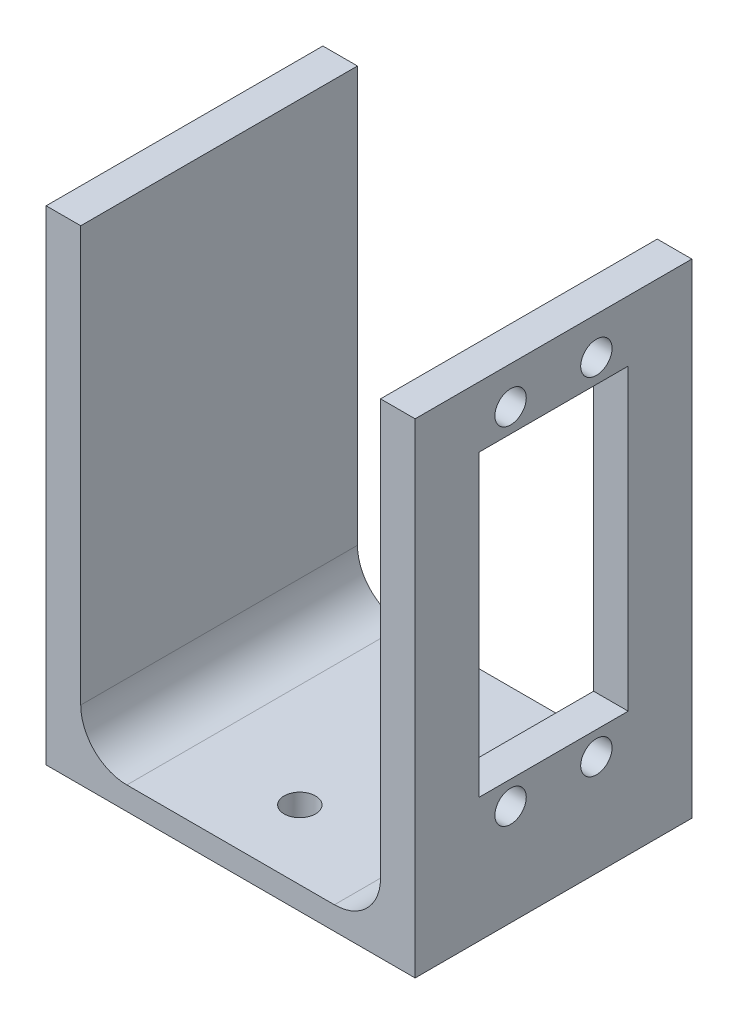
SolidWorks part; units mm, degrees
ref_plane "Front" through (0, 0, 0) normal (0, 0, 1) x (1, 0, 0)
ref_plane "Top" through (0, 0, 0) normal (0, 1, 0) x (1, 0, 0)
ref_plane "Right" through (0, 0, 0) normal (1, 0, 0) x (0, 0, -1)
sketch "Sketch1" plane through (0, 0, 0) normal (0, 1, 0) x (1, 0, 0)
  line L1 (0, 0) -> (50.8, 0)
  line L2 (0, 0) -> (0, 38.1)
  line L3 (0, 38.1) -> (50.8, 38.1)
  line L4 (50.8, 0) -> (50.8, 38.1)
  dimension "D1" = 38.1
  dimension "D2" = 50.8
extrude "Boss-Extrude1" add sketch "Sketch1" along normal blind 3.175
sketch "Sketch2" plane through (0, 3.175, 0) normal (0, 1, 0) x (1, 0, 0)
  line L0 (0, 0) -> (50.8, 0) construction
  line L1 (50.8, 38.1) -> (46.0375, 38.1)
  line L2 (50.8, 38.1) -> (50.8, 0)
  line L3 (50.8, 0) -> (46.0375, 0)
  line L4 (46.0375, 38.1) -> (46.0375, 0)
  line L5 (50.8, 38.1) -> (0, 38.1) construction
  line L6 (4.7625, 38.1) -> (0, 38.1)
  line L7 (4.7625, 38.1) -> (4.7625, 0)
  line L8 (4.7625, 0) -> (0, 0)
  line L9 (0, 38.1) -> (0, 0)
  dimension "D1" = 4.7625
extrude "Boss-Extrude2" add sketch "Sketch2" along normal blind 63.5
fillet "Fillet1" radius 6.35 2 edges at (4.7625, 3.175, -19.05) (46.0375, 3.175, -19.05)
sketch "Sketch3" plane through (50.8, 0, 0) normal (1, 0, 0) x (0, 0, -1)
  line L0 (0, 0) -> (38.1, 0) construction
  line L1 (38.1, 66.675) -> (38.1, 0) construction
  line L2 (0, 66.675) -> (38.1, 66.675) construction
  line L5 (8.763, 58.293) -> (29.337, 58.293)
  line L6 (8.763, 58.293) -> (8.763, 17.145)
  line L7 (8.763, 17.145) -> (29.337, 17.145)
  line L8 (29.337, 58.293) -> (29.337, 17.145)
  point P0 (19.05, 10.3505)
  point P8 (19.05, 65.0875)
  point P9 (19.05, 66.675)
  point P14 (19.05, 17.145)
  point P15 (29.337, 37.719)
  point P16 (28.8925, 37.719)
  line B0 (28.8925, 65.0875) -> (28.8925, 10.3505) construction
  line B1 (28.8925, 65.0875) -> (9.2075, 65.0875) construction
  line B2 (9.2075, 65.0875) -> (9.2075, 10.3505) construction
  circle B3 centre (24.9555, 61.5315) radius 2.159
  circle B4 centre (13.1445, 61.5315) radius 2.159
  circle B5 centre (13.1445, 13.9065) radius 2.159
  circle B6 centre (24.9555, 13.9065) radius 2.159
  dimension "D1" = 1.5875
  dimension "D2" = 41.148
  dimension "D3" = 20.574
sketch_block_instance "ServoMountingHoles-1"
sketch_block "ServoMountingHoles"
extrude "Cut-Extrude1" cut sketch "Sketch3" against normal up to next
sketch "Sketch4" plane through (0, 3.175, 0) normal (0, 1, 0) x (1, 0, 0)
  line L0 (25.4, 28.575) -> (25.4, 9.525) construction
  line L1 (11.1125, 19.05) -> (39.6875, 19.05) construction
  line L2 (11.1125, 38.1) -> (11.1125, 0) construction
  line L3 (39.6875, 0) -> (39.6875, 38.1) construction
  circle A0 centre (25.4, 28.575) radius 2.159
  circle A1 centre (25.4, 9.525) radius 2.159
  point P10 (25.4, 19.05)
  dimension "D1" = 19.05
  dimension "D2" = 4.318
extrude "Cut-Extrude2" cut sketch "Sketch4" against normal up to next
